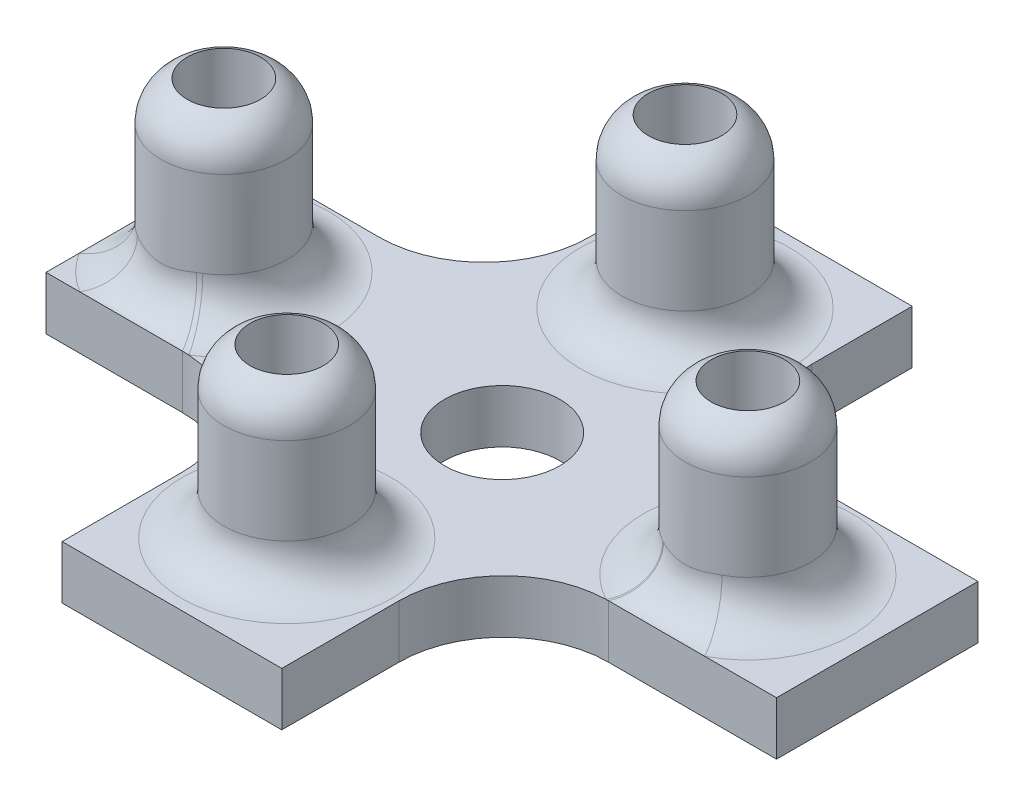
SolidWorks part; units mm, degrees
ref_plane "Front Plane" through (0, 0, 0) normal (0, 0, 1) x (1, 0, 0)
ref_plane "Top Plane" through (0, 0, 0) normal (0, 1, 0) x (1, 0, 0)
ref_plane "Right Plane" through (0, 0, 0) normal (1, 0, 0) x (0, 0, -1)
sketch "Sketch1" plane through (0, 0, 0) normal (0, 1, 0) x (1, 0, 0)
  line L0 (-17.5, 5.1389) -> (-5.9954, 5.1389)
  line L1 (-17.5, -15) -> (17.5, -15)
  line L2 (-17.5, -15) -> (-17.5, 15)
  line L3 (-17.5, 15) -> (17.5, 15)
  line L4 (17.5, -15) -> (17.5, 15)
  line L5 (-17.5, -15) -> (17.5, 15) construction
  line L6 (-17.5, 15) -> (17.5, -15) construction
  line L7 (-5.9954, 5.1389) -> (-5.9954, 15)
  line L8 (-5.9954, 15) -> (4.5622, 15)
  line L9 (4.5622, 15) -> (4.5622, 5.2006)
  line L10 (4.5622, 5.2006) -> (17.5, 5.2006)
  line L11 (17.5, 5.2006) -> (17.5, -4.412)
  line L12 (17.5, -4.412) -> (4.4871, -4.412)
  line L13 (4.4871, -4.412) -> (4.4871, -15)
  line L14 (4.4871, -15) -> (-5.9954, -15)
  line L15 (-5.9954, -15) -> (-5.9954, -4.2618)
  line L16 (-5.9954, -4.2618) -> (-17.5, -4.2618)
  line L17 (-17.5, -4.2618) -> (-17.5, 5.1389)
  circle A0 centre (-0.7771, 9.5) radius 1.75
  circle A1 centre (11.7229, 0) radius 1.75
  circle A2 centre (-0.7771, -9.5) radius 1.75
  circle A3 centre (-13.2771, 0) radius 1.75
  circle A4 centre (-13.2771, 0) radius 3
  circle A5 centre (-0.7771, 9.5) radius 3
  circle A6 centre (11.7229, 0) radius 3
  circle A7 centre (-0.7771, -9.5) radius 3
  circle A8 centre (0, 0) radius 2.75
  point P0 (0, 0)
  point P24 (-0.7771, 0)
  point P35 (0, 0)
  point P36 (-17.5, 0)
  point P37 (0, 0)
  point P38 (0, 0)
  point P39 (17.5, 0)
  point P43 (-17.5, 5.5761)
  dimension "D1" = 3.5
  dimension "D2" = 3.5
  dimension "D3" = 3.5
  dimension "D4" = 3.5
  dimension "D7" = 6
  dimension "D8" = 6
  dimension "D9" = 6
  dimension "D10" = 6
  dimension "D11" = 5.5
  dimension "D5" = 35
  dimension "D6" = 30
extrude "Boss-Extrude1" add sketch "Sketch1" along normal mid plane 2.54 contours L16 L15 L1 L13 L12 L4 L10 L9 L3 L7 L0 L2 A7 A6 A5 A4 | A4 A3 | A5 A0 | A6 A1 | A7 A2 region at (-11.7477, 0, -4.6779) region at (-16.1923, 0, 0) region at (-3.6923, 0, -9.5) region at (8.8077, 0, 0) region at (-3.6923, 0, 9.5)
extrude "Boss-Extrude2" add sketch "Sketch1<3>" along normal blind 8 from surface contours A4 A3 | A7 A2 | A6 A1 | A5 A0 region at (-16.1923, 0, 0) region at (-3.6923, 0, -9.5) region at (8.8077, 0, 0) region at (-3.6923, 0, 9.5) starting at face at (0, 1.27, 2.75)
sketch "Sketch1<3>" plane through (0, 0, 0) normal (0, 1, 0) x (1, 0, 0) same geometry as "Sketch1"
fillet "Fillet1" radius 5 4 edges at (-5.9954, 0, 4.2618) (4.4871, 0, 4.412) (4.5622, 0, -5.2006) (-5.9954, 0, -5.1389)
fillet "Fillet2" radius 2 8 edges at (-0.7771, 1.27, -6.5) (-0.7771, 9.27, -6.5) (-0.7771, 1.27, 12.5) (-0.7771, 9.27, 12.5) (-13.2771, 1.27, 3) (-13.2771, 9.27, 3) (11.7229, 1.27, 3) (11.7229, 9.27, 3)
